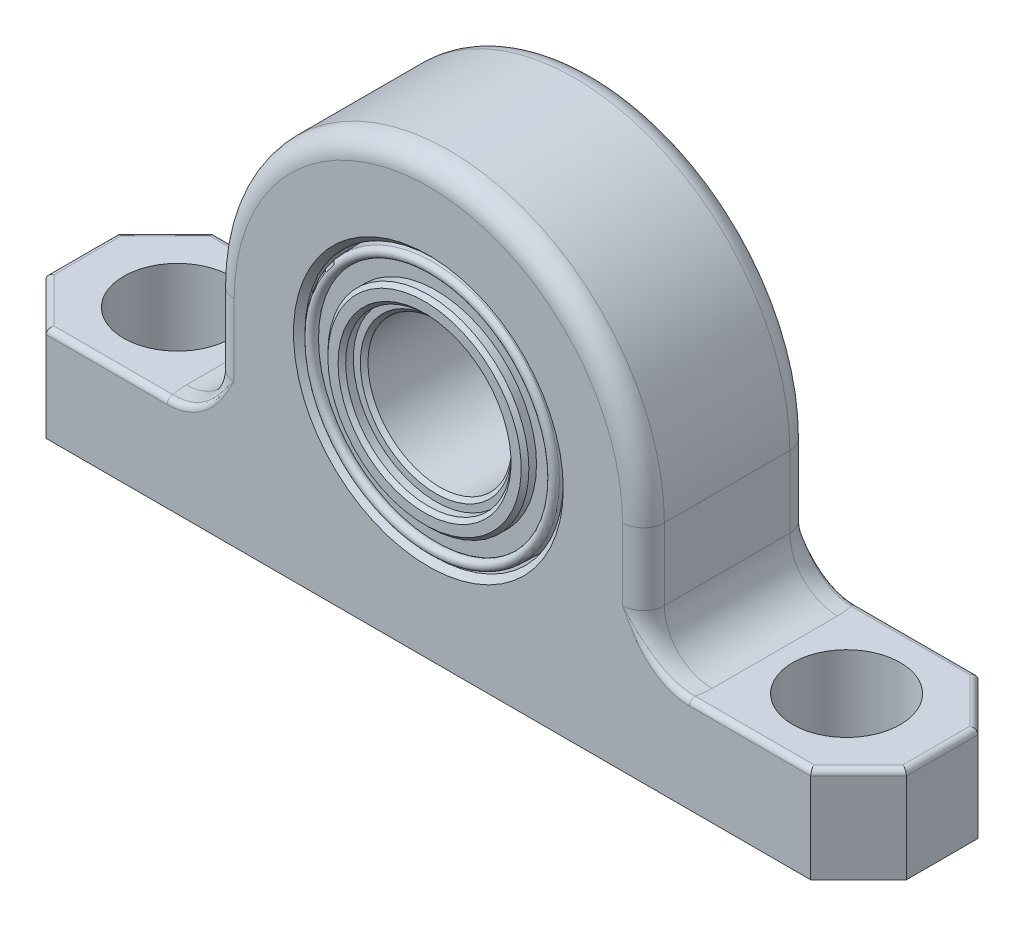
SolidWorks part; units mm, degrees
ref_plane "Front Plane" through (0, 0, 0) normal (0, 0, 1) x (1, 0, 0)
ref_plane "Top Plane" through (0, 0, 0) normal (0, 1, 0) x (1, 0, 0)
ref_plane "Right Plane" through (0, 0, 0) normal (1, 0, 0) x (0, 0, -1)
sketch "Sketch1" plane through (0, 0, 0) normal (0, 0, 1) x (1, 0, 0)
  line L0 (-28.575, 0) -> (28.575, 0)
  line L1 (28.575, 0) -> (28.575, 6.35)
  line L2 (-28.575, 0) -> (-28.575, 6.35)
  line L3 (-28.575, 6.35) -> (-14.2875, 6.35)
  line L4 (28.575, 6.35) -> (14.2875, 6.35)
  line L5 (-14.2875, 6.35) -> (-14.2875, 14.2875)
  line L6 (14.2875, 6.35) -> (14.2875, 14.2875)
  line L7 (0, 0) -> (0, 28.575) construction
  line L8 (3.3766, 17.6641) -> (10.1028, 24.3903) construction
  line L9 (3.3766, 17.6641) -> (4.7218, 19.0093) construction
  line L10 (4.7218, 19.0093) -> (6.0671, 20.3546) construction
  line L11 (6.0671, 20.3546) -> (7.4123, 21.6998) construction
  line L12 (7.4123, 21.6998) -> (8.7575, 23.045) construction
  line L13 (8.7575, 23.045) -> (10.1028, 24.3903) construction
  circle A0 centre (0, 14.2875) radius 4.7752
  arc A1 (14.2875, 14.2875) -> (-14.2875, 14.2875) centre (0, 14.2875) ccw
  circle A2 centre (0, 14.2875) radius 8.5801 construction
  point P16 (6.0671, 20.3546)
  point P17 (0, 19.0627)
  point P18 (0, 22.8676)
  dimension "ID" = 9.5504
  dimension "Overall Height" = 28.575
  dimension "Overall Length" = 57.15
  dimension "CAD B" = 6.35
  dimension "Center Height" = 14.2875
  dimension "D1" = 45
sketch "Sketch2" plane through (0, 0, 0) normal (0, 1, 0) x (1, 0, 0)
  line L0 (-22.225, 0) -> (22.225, 0) construction
  line L1 (-28.575, -5.5562) -> (28.575, 5.5562) construction
  line L2 (-28.575, 5.5562) -> (28.575, 5.5562)
  line L3 (-28.575, 5.5562) -> (-28.575, -5.5562)
  line L4 (-28.575, -5.5562) -> (28.575, -5.5562)
  line L5 (28.575, 5.5562) -> (28.575, -5.5562)
  circle A0 centre (-22.225, 0) radius 3.5719
  circle A1 centre (22.225, 0) radius 3.5719
sketch "Sketch3" plane through (0, 0, 0) normal (0, 0, 1) x (1, 0, 0)
  line L0 (-28.575, 0) -> (-28.575, 6.35) construction
  line L1 (-28.575, 0) -> (28.575, 0) construction
  line L2 (-28.575, 6.35) -> (-14.2875, 6.35) construction
  line L3 (28.575, 6.35) -> (14.2875, 6.35) construction
  line L4 (28.575, 0) -> (28.575, 6.35) construction
  line L5 (14.2875, 6.35) -> (14.2875, 14.2875) construction
  line L6 (-14.2875, 6.35) -> (-14.2875, 14.2875) construction
  line L7 (-28.575, 0) -> (-28.575, 6.35)
  line L8 (-28.575, 0) -> (28.575, 0)
  line L9 (-28.575, 6.35) -> (-14.2875, 6.35)
  line L10 (28.575, 6.35) -> (14.2875, 6.35)
  line L11 (28.575, 0) -> (28.575, 6.35)
  line L12 (14.2875, 6.35) -> (14.2875, 14.2875)
  line L13 (-14.2875, 6.35) -> (-14.2875, 14.2875)
  arc A0 (14.2875, 14.2875) -> (-14.2875, 14.2875) centre (0, 14.2875) ccw construction
  circle A1 centre (0, 14.2875) radius 8.5801 construction
  arc A2 (14.2875, 14.2875) -> (-14.2875, 14.2875) centre (0, 14.2875) ccw
  circle A3 centre (0, 14.2875) radius 8.5801
extrude "Boss-Extrude1" add sketch "Sketch3" against normal up to vertex (5.5563 mm away) and the other way up to vertex (5.5563 mm away) up to point (-28.575, 0, -5.5562) other way up to point (-28.575, 0, 5.5562)
sketch "Sketch4" plane through (0, 0, 0) normal (0, 1, 0) x (1, 0, 0)
  circle A0 centre (-22.225, 0) radius 3.5719 construction
  circle A1 centre (22.225, 0) radius 3.5719 construction
  circle A2 centre (-22.225, 0) radius 3.5719
  circle A3 centre (22.225, 0) radius 3.5719
extrude "Cut-Extrude1" cut sketch "Sketch4" along normal through all
chamfer "Chamfer1" distance 3.175 angle 45 4 edges at (-28.575, 3.175, -5.5562) (28.575, 3.175, 5.5562) (28.575, 3.175, -5.5562) (-28.575, 3.175, 5.5562)
fillet "Fillet1" radius 1.3891 6 edges at (-14.2875, 10.3188, -5.5562) (0, 28.575, -5.5562) (-14.2875, 10.3188, 5.5562) (0, 28.575, 5.5562) (14.2875, 10.3187, -5.5562) (14.2875, 10.3187, 5.5562)
fillet "Fillet2" radius 3.175 6 edges at (-13.8807, 6.35, -5.1494) (-13.8807, 6.35, 5.1494) (13.8807, 6.35, -5.1494) (13.8807, 6.35, 5.1494) (-14.2875, 6.35, 0) (14.2875, 6.35, 0)
chamfer "Chamfer2" distance 0.381 angle 45 2 edges at (8.5801, 14.2875, 5.5562) (8.5801, 14.2875, -5.5562)
fillet "Fillet3" radius 0.381 14 edges at (-15.0119, 7.0879, -5.5562) (-15.0119, 7.0879, 5.5562) (15.0119, 7.0879, -5.5562) (15.0119, 7.0879, 5.5562) (-21.323, 6.35, -5.5562) (-26.9875, 6.35, -3.9687) (-28.575, 6.35, 0) (-26.9875, 6.35, 3.9687) (-21.323, 6.35, 5.5562) (21.323, 6.35, -5.5562) (26.9875, 6.35, -3.9687) (28.575, 6.35, 0) (26.9875, 6.35, 3.9687) (21.323, 6.35, 5.5562)
sketch "Sketch5" plane through (0, 0, 0) normal (1, 0, 0) x (0, 0, -1)
  line L1 (-5.5563, 22.8676) -> (5.5562, 22.8676)
  line L2 (-5.5563, 22.8676) -> (-5.5563, 19.0627)
  line L3 (-5.5563, 19.0627) -> (5.5562, 19.0627)
  line L4 (5.5562, 22.8676) -> (5.5562, 19.0627)
sketch "Sketch6" plane through (0, 0, 0) normal (1, 0, 0) x (0, 0, -1)
  line L0 (0, 22.8676) -> (5.5562, 22.8676)
  line L1 (0, 19.0627) -> (0, 19.6969) construction
  line L2 (0, 22.8676) -> (-5.2432, 22.6845)
  line L3 (-5.5563, 22.8676) -> (-5.5563, 19.0627) construction
  line L4 (-5.0483, 22.0929) -> (-5.0483, 20.9652)
  line L5 (-5.0483, 20.9652) -> (-5.8103, 20.9652)
  line L6 (-5.8103, 20.9652) -> (-5.8103, 19.779)
  line L7 (-5.8103, 19.779) -> (-5.0483, 19.779)
  line L8 (-5.0483, 19.779) -> (-5.0483, 19.0627)
  line L9 (-5.5563, 19.0627) -> (5.5562, 19.0627) construction
  line L10 (-5.0483, 19.0627) -> (3.5242, 19.0627)
  line L11 (5.5562, 22.8676) -> (5.5562, 22.0929)
  line L12 (5.5562, 22.8676) -> (5.5562, 19.0627) construction
  line L13 (5.5562, 22.0929) -> (1.7462, 22.0929)
  line L14 (1.7462, 22.0929) -> (1.7462, 20.9652)
  line L15 (1.7462, 20.9652) -> (4.2862, 20.9652)
  line L16 (4.2862, 20.9652) -> (4.2862, 19.779)
  line L17 (4.2862, 19.779) -> (3.5242, 19.779)
  line L18 (3.5242, 19.779) -> (3.5242, 19.0627)
  line L19 (0, 0) -> (0, 28.575) construction
  line L20 (-5.5562, 14.2875) -> (5.5562, 14.2875) construction
  line L21 (-5.5562, 0) -> (-5.5562, 5.969) construction
  line L22 (0, 19.6969) -> (0, 20.331) construction
  line L23 (0, 20.331) -> (0, 20.9652) construction
  line L24 (0, 20.9652) -> (0, 21.5993) construction
  line L25 (0, 21.5993) -> (0, 22.2335) construction
  line L26 (0, 22.2335) -> (0, 22.8676) construction
  line L27 (-5.0483, 20.9652) -> (1.7462, 20.9652) construction
  arc A0 (-5.2432, 22.6845) -> (-5.0483, 22.0929) centre (-5.2319, 22.3603) ccw
  dimension "D8" = 0.3244
  dimension "D1" = 2
  dimension "D2" = 0.254
  dimension "D3" = 0.762
  dimension "D5" = 1.27
  dimension "D6" = 2.54
  dimension "D9" = 10.983
revolve "Revolve1" add sketch "Sketch6" angle 360 about L20
chamfer "Chamfer3" distance 0.254 angle 45 6 edges at (5.4915, 14.2875, -4.2862) (6.6777, 14.2875, -4.2862) (4.7752, 14.2875, 5.0483) (4.7752, 14.2875, -3.5242) (6.6777, 14.2875, 5.8103) (5.4915, 14.2875, 5.8103)
equation "\"D1@Fillet1\"=\"Overall Width@Sketch2\"/8"
equation "\"D9@Sketch6\"=\"ID@Sketch1\"*1.15"
